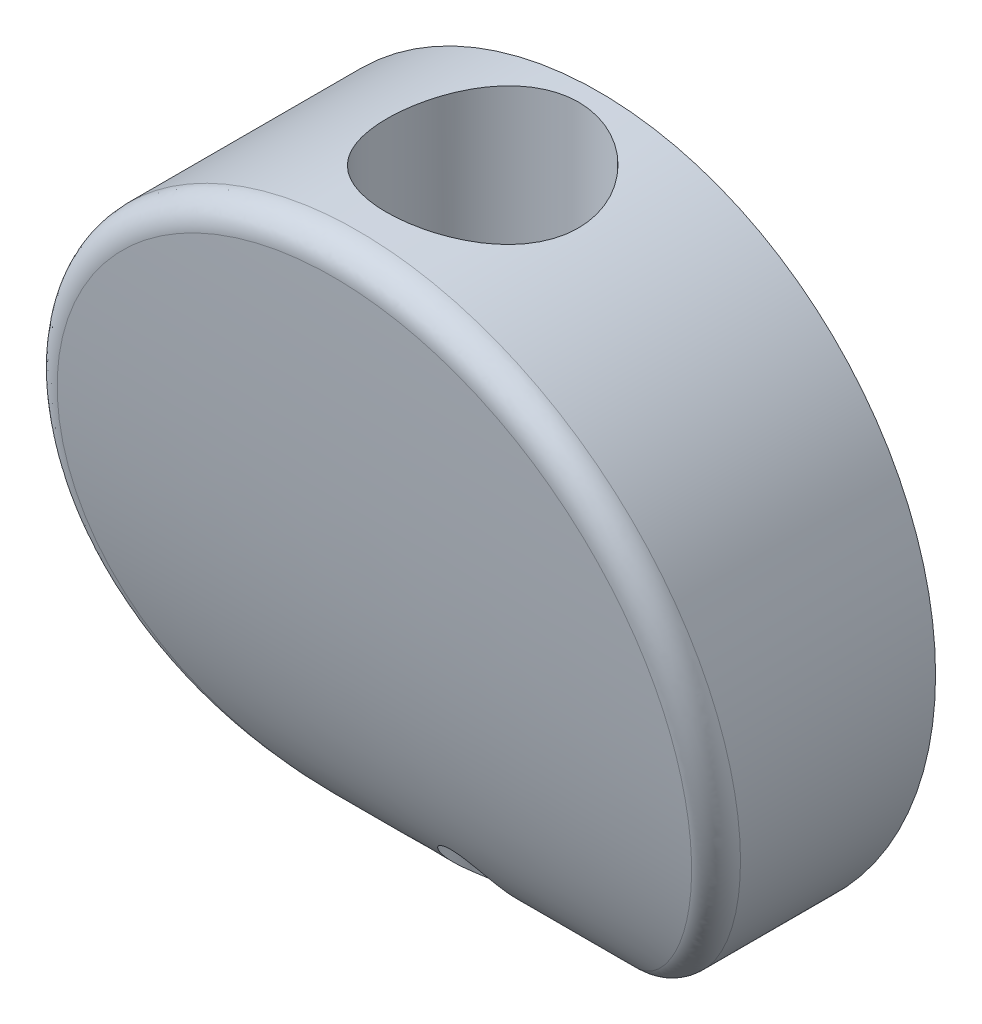
SolidWorks part; units mm, degrees
ref_plane "Plan de face" through (0, 0, 0) normal (0, 0, 1) x (1, 0, 0)
ref_plane "Plan de dessus" through (0, 0, 0) normal (0, 1, 0) x (1, 0, 0)
ref_plane "Plan de droite" through (0, 0, 0) normal (1, 0, 0) x (0, 0, -1)
sketch "Esquisse1" plane through (0, 0, 0) normal (0, 0, 1) x (1, 0, 0)
  circle A0 centre (0.2907, 0.2907) radius 67
  dimension "D1" = 134
extrude "Boss.-Extru.1" add sketch "Esquisse1" along normal blind 53.34
sketch "Esquisse4" plane through (0, 0, 0) normal (1, 0, 0) x (0, 0, -1)
  line L1 (-0.1422, -67.1272) -> (-53.34, -66.7093)
  line L2 (-53.34, -66.7093) -> (-53.34, 67.2907)
  spline S0 degree 3 poles (-53.34, 67.2907) (-53.3149, 64.9653) (-44.6519, -34.8903) (-23.1604, -66.3734) (-0.1422, -67.1272) knots 0 0 0 0 0.36297 1 1 1 1
  point P3 (0, 0)
  point P4 (-20.7566, -28.5025)
  point P6 (0, 0)
  point P7 (0, 0)
  point P8 (0, 0)
  point P9 (0, 0)
  point P10 (0, 0)
  point P12 (-22.587, -27.4979)
  point P13 (-50.4672, -28.6441)
  point P14 (-0.0673, -33.6245)
  point P15 (-30.8136, -27.9127)
  point P17 (-44.0854, 2.4461)
  point P18 (-45.336, 1.4841)
  point P19 (-0.4302, -66.1223)
  point P20 (0, 0)
  point P21 (0, 0)
  point P22 (0, 0)
  point P23 (-0.1422, -67.1272)
extrude "Enlèv. mat.-Extru.1" cut sketch "Esquisse4" against normal through all both and the other way through all
fillet "Congé1" radius 5 1 edges at (-0.0427, -66.7085, 4.6747)
sketch "Esquisse5" plane through (0, 0, 0) normal (0, 1, 0) x (1, 0, 0)
  line L0 (67.2907, 0) -> (-66.7093, 0) construction
  circle A0 centre (0, -22.86) radius 19.05
  point P2 (0, 0)
  point P4 (0, 0)
  point P5 (0, -22.2404)
  dimension "D1" = 38.1
  dimension "D2" = 22.86
extrude "Enlèv. mat.-Extru.2" cut sketch "Esquisse5" along normal up to next and the other way blind 3.81
sketch "Esquisse6" plane through (0, -3.81, 0) normal (0, 1, 0) x (1, 0, 0)
  circle A0 centre (0, -22.86) radius 6.35
  circle A1 centre (0, -22.86) radius 19.05 construction
  dimension "D1" = 12.7
extrude "Enlèv. mat.-Extru.3" cut sketch "Esquisse6" against normal through all
